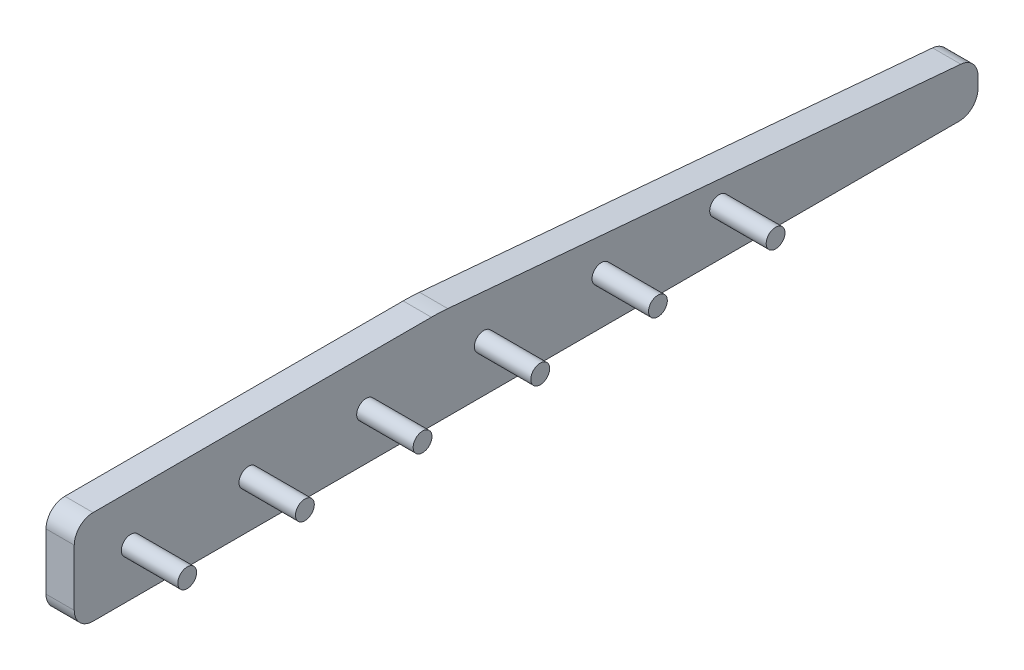
SolidWorks part; units mm, degrees
material "Cast Carbon Steel"
ref_plane "Front Plane" through (0, 0, 0) normal (0, 0, 1) x (1, 0, 0)
ref_plane "Top Plane" through (0, 0, 0) normal (0, 1, 0) x (1, 0, 0)
ref_plane "Right Plane" through (0, 0, 0) normal (1, 0, 0) x (0, 0, -1)
sketch "Sketch1" plane through (0, 0, 0) normal (0, 0, 1) x (1, 0, 0)
  line L0 (50.8, 0) -> (254, 0) construction
  line L1 (304.8, 50.8) -> (304.8, 121.2817) construction
  line L2 (355.6, 172.0817) -> (723.9, 172.0817) construction
  line L3 (774.7, 222.8817) -> (774.7, 375.2817) construction
  line L4 (723.9, 426.0817) -> (355.6, 426.0817) construction
  line L5 (304.8, 375.2817) -> (304.8, 355.6) construction
  line L6 (254, 304.8) -> (50.8, 304.8) construction
  line L7 (0, 254) -> (0, 50.8) construction
  line L9 (304.8, 304.8) -> (228.6, 304.8)
  line L10 (304.8, 304.8) -> (304.8, 50.8)
  line L11 (304.8, 50.8) -> (228.6, 50.8)
  line L12 (228.6, 304.8) -> (228.6, 50.8)
  arc A0 (355.6, 426.0817) -> (304.8, 375.2817) centre (355.6, 375.2817) ccw construction
  arc A1 (774.7, 375.2817) -> (723.9, 426.0817) centre (723.9, 375.2817) ccw construction
  arc A2 (723.9, 172.0817) -> (774.7, 222.8817) centre (723.9, 222.8817) ccw construction
  arc A3 (254, 0) -> (304.8, 50.8) centre (254, 50.8) ccw construction
  arc A4 (50.8, 0) -> (0, 50.8) centre (50.8, 50.8) cw construction
  arc A5 (304.8, 121.2817) -> (355.6, 172.0817) centre (355.6, 121.2817) cw construction
  arc A6 (50.8, 304.8) -> (0, 254) centre (50.8, 254) ccw construction
  arc A7 (304.8, 355.6) -> (254, 304.8) centre (254, 355.6) cw construction
  point P11 (304.8, 426.0817)
  point P14 (774.7, 426.0817)
  point P17 (774.7, 172.0817)
  point P20 (304.8, 0)
  point P23 (0, 0)
  point P26 (304.8, 172.0817)
  point P29 (0, 304.8)
  point P32 (304.8, 304.8)
  dimension "D5" = 50.8
  dimension "D1" = 304.8
  dimension "D2" = 304.8
  dimension "D3" = 469.9
  dimension "D4" = 254
  dimension "D6" = 0
  dimension "D7" = 76.2
extrude "Boss-Extrude1" add sketch "Sketch1" along normal blind 2438.4
sketch "Sketch2" plane through (304.8, 0, 0) normal (1, 0, 0) x (0, 0, -1)
  line L0 (0, 177.8) -> (-1452.626, 304.8)
  line L1 (0, 50.8) -> (0, 304.8) construction
  line L2 (-2438.4, 304.8) -> (0, 304.8) construction
  line L3 (-1452.626, 304.8) -> (0, 304.8)
  line L4 (0, 304.8) -> (0, 177.8)
  dimension "D1" = 1452.626
extrude "Cut-Extrude1" cut sketch "Sketch2" against normal through all
fillet "Fillet1" radius 50.8 4 edges at (266.7, 304.8, 2438.4) (266.7, 50.8, 2438.4) (266.7, 50.8, 0) (266.7, 177.8, 0)
fillet "Fillet2" radius 508 1 edges at (266.7, 304.8, 1452.626)
sketch "Sketch3" plane through (304.8, 0, 0) normal (1, 0, 0) x (0, 0, -1)
  line L0 (-2438.4, 101.6) -> (-2438.4, 254) construction
  circle A0 centre (-2286, 177.8) radius 25.4
  point P6 (-2438.4, 177.8)
  dimension "D1" = 50.8
  dimension "D2" = 152.4
extrude "Boss-Extrude2" add sketch "Sketch3" along normal blind 152.4
pattern_linear "LPattern1" count 6 spacing 317.5 along (0, 0, -1) of "Boss-Extrude2"
ref_plane "Plane1" through (266.7, 0, 0) normal (1, 0, 0) x (0, 0, -1)
